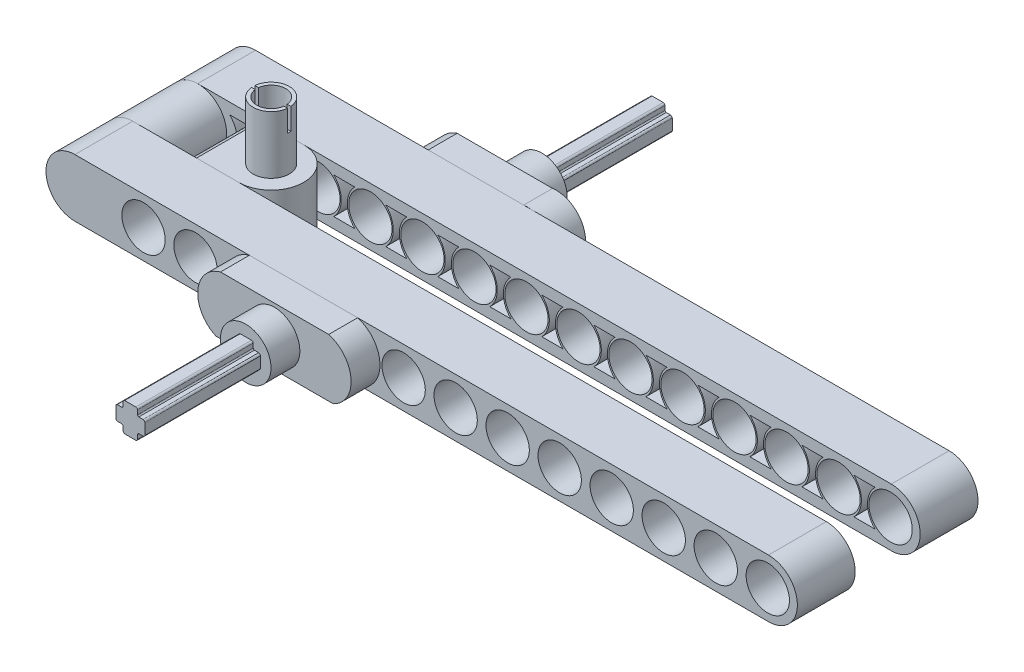
SolidWorks part; units mm, degrees
ref_plane "Front Plane" through (0, 0, 0) normal (0, 0, 1) x (1, 0, 0)
ref_plane "Top Plane" through (0, 0, 0) normal (0, 1, 0) x (1, 0, 0)
ref_plane "Right Plane" through (0, 0, 0) normal (1, 0, 0) x (0, 0, -1)
sketch "Sketch1" plane through (0, 0, 0) normal (0, 0, 1) x (1, 0, 0)
  line L1 (48, 4) -> (-48, 4)
  line L3 (48, -4) -> (-48, -4)
  line L5 (48, 4) -> (-48, -4) construction
  line L6 (48, -4) -> (-48, 4) construction
  arc A0 (48, -4) -> (48, 4) centre (48, 0) ccw
  arc A1 (-48, 4) -> (-48, -4) centre (-48, 0) ccw
  point P0 (0, 0)
  dimension "D1" = 96
  dimension "D2" = 8
extrude "Boss-Extrude1" add sketch "Sketch1" against normal blind 8
sketch "Sketch2" plane through (0, 0, 0) normal (0, 0, 1) x (1, 0, 0)
  circle A0 centre (-48, 0) radius 4
  dimension "D1" = 8
extrude "Boss-Extrude2" add sketch "Sketch2" along normal blind 9 separate body
sketch "Sketch3" plane through (0, 0, 9) normal (0, 0, 1) x (1, 0, 0)
  line L0 (48, 4) -> (-48, 4)
  line L1 (48, -4) -> (-48, -4)
  line L2 (48, 4) -> (-48, -4) construction
  line L3 (48, -4) -> (-48, 4) construction
  arc A0 (48, -4) -> (48, 4) centre (48, 0) ccw
  arc A1 (-48, 4) -> (-48, -4) centre (-48, 0) ccw
  point P0 (0, 0)
  dimension "D1" = 96
  dimension "D2" = 8
extrude "Boss-Extrude3" add sketch "Sketch3" along normal blind 8 separate body
sketch "Sketch4" plane through (0, 0, 0) normal (0, 0, 1) x (1, 0, 0)
  line L0 (-48, -4) -> (48, -4) construction
  line L1 (-39.9427, 3) -> (-42.8574, 3)
  line L2 (-39.9427, -3) -> (-42.8574, -3)
  line L3 (-32.7427, 3) -> (-35.6574, 3)
  line L4 (-32.7427, -3) -> (-35.6574, -3)
  line L5 (-25.5427, 3) -> (-28.4574, 3)
  line L6 (-25.5427, -3) -> (-28.4574, -3)
  line L7 (-18.3427, 3) -> (-21.2574, 3)
  line L8 (-18.3427, -3) -> (-21.2574, -3)
  line L9 (-11.1427, 3) -> (-14.0574, 3)
  line L10 (-11.1427, -3) -> (-14.0574, -3)
  line L11 (-3.9427, 3) -> (-6.8574, 3)
  line L12 (-3.9427, -3) -> (-6.8574, -3)
  line L13 (3.2573, 3) -> (0.3426, 3)
  line L14 (3.2573, -3) -> (0.3426, -3)
  line L15 (10.4573, 3) -> (7.5426, 3)
  line L16 (10.4573, -3) -> (7.5426, -3)
  line L17 (17.6573, 3) -> (14.7426, 3)
  line L18 (17.6573, -3) -> (14.7426, -3)
  line L19 (24.8573, 3) -> (21.9426, 3)
  line L20 (24.8573, -3) -> (21.9426, -3)
  line L21 (32.0573, 3) -> (29.1426, 3)
  line L22 (32.0573, -3) -> (29.1426, -3)
  line L23 (39.2573, 3) -> (36.3426, 3)
  line L24 (39.2573, -3) -> (36.3426, -3)
  line L25 (46.4573, 3) -> (43.5426, 3)
  line L26 (46.4573, -3) -> (43.5426, -3)
  circle A0 centre (-38.5, 0) radius 3
  circle A1 centre (-48, 0) radius 4 construction
  arc A2 (-42.8574, 3) -> (-42.8574, -3) centre (-44.7282, 0) cw
  arc A3 (-39.9427, 3) -> (-39.9427, -3) centre (-38.0718, 0) ccw
  circle A4 centre (-31.3, 0) radius 3
  arc A5 (-35.6574, 3) -> (-35.6574, -3) centre (-37.5282, 0) cw
  arc A6 (-32.7427, 3) -> (-32.7427, -3) centre (-30.8718, 0) ccw
  circle A7 centre (-24.1, 0) radius 3
  arc A8 (-28.4574, 3) -> (-28.4574, -3) centre (-30.3282, 0) cw
  arc A9 (-25.5427, 3) -> (-25.5427, -3) centre (-23.6718, 0) ccw
  circle A10 centre (-16.9, 0) radius 3
  arc A11 (-21.2574, 3) -> (-21.2574, -3) centre (-23.1282, 0) cw
  arc A12 (-18.3427, 3) -> (-18.3427, -3) centre (-16.4718, 0) ccw
  circle A13 centre (-9.7, 0) radius 3
  arc A14 (-14.0574, 3) -> (-14.0574, -3) centre (-15.9282, 0) cw
  arc A15 (-11.1427, 3) -> (-11.1427, -3) centre (-9.2718, 0) ccw
  circle A16 centre (-2.5, 0) radius 3
  arc A17 (-6.8574, 3) -> (-6.8574, -3) centre (-8.7282, 0) cw
  arc A18 (-3.9427, 3) -> (-3.9427, -3) centre (-2.0718, 0) ccw
  circle A19 centre (4.7, 0) radius 3
  arc A20 (0.3426, 3) -> (0.3426, -3) centre (-1.5282, 0) cw
  arc A21 (3.2573, 3) -> (3.2573, -3) centre (5.1282, 0) ccw
  circle A22 centre (11.9, 0) radius 3
  arc A23 (7.5426, 3) -> (7.5426, -3) centre (5.6718, 0) cw
  arc A24 (10.4573, 3) -> (10.4573, -3) centre (12.3282, 0) ccw
  circle A25 centre (19.1, 0) radius 3
  arc A26 (14.7426, 3) -> (14.7426, -3) centre (12.8718, 0) cw
  arc A27 (17.6573, 3) -> (17.6573, -3) centre (19.5282, 0) ccw
  circle A28 centre (26.3, 0) radius 3
  arc A29 (21.9426, 3) -> (21.9426, -3) centre (20.0718, 0) cw
  arc A30 (24.8573, 3) -> (24.8573, -3) centre (26.7282, 0) ccw
  circle A31 centre (33.5, 0) radius 3
  arc A32 (29.1426, 3) -> (29.1426, -3) centre (27.2718, 0) cw
  arc A33 (32.0573, 3) -> (32.0573, -3) centre (33.9282, 0) ccw
  circle A34 centre (40.7, 0) radius 3
  arc A35 (36.3426, 3) -> (36.3426, -3) centre (34.4718, 0) cw
  arc A36 (39.2573, 3) -> (39.2573, -3) centre (41.1282, 0) ccw
  circle A37 centre (47.9, 0) radius 3
  arc A38 (43.5426, 3) -> (43.5426, -3) centre (41.6718, 0) cw
  arc A39 (46.4573, 3) -> (46.4573, -3) centre (48.3282, 0) ccw
  point P12 (-41.6074, 0)
  dimension "D1" = 6
  dimension "D4" = 3.5355
  dimension "D6" = 3.5355
  dimension "D2" = 9.5
  dimension "D3" = 4
  dimension "D5" = 3.1074
  dimension "D7" = 2.9147
  dimension "D9" = 7.2
  dimension "D8" = 13
extrude "Cut-Extrude4" cut sketch "Sketch4" against normal through all both and the other way through all contours A0 | A4 | A7 | A16 | A13 | A10 | A19 | A22 | A25 | A28 | A34 | A31 | A37
sketch "Sketch12" plane through (0, 0, 0) normal (0, 0, 1) x (1, 0, 0)
  line L0 (-40.6568, 2.4796) -> (-43.5715, 2.4796)
  line L1 (-40.6568, -2.5204) -> (-43.5715, -2.5204)
  line L2 (-33.4568, 2.4796) -> (-36.3715, 2.4796)
  line L3 (-33.4568, -2.5204) -> (-36.3715, -2.5204)
  line L4 (-26.2568, 2.4796) -> (-29.1715, 2.4796)
  line L5 (-26.2568, -2.5204) -> (-29.1715, -2.5204)
  line L6 (-19.0568, 2.4796) -> (-21.9715, 2.4796)
  line L7 (-19.0568, -2.5204) -> (-21.9715, -2.5204)
  line L8 (-11.8568, 2.4796) -> (-14.7715, 2.4796)
  line L9 (-11.8568, -2.5204) -> (-14.7715, -2.5204)
  line L10 (-4.6568, 2.4796) -> (-7.5715, 2.4796)
  line L11 (-4.6568, -2.5204) -> (-7.5715, -2.5204)
  line L12 (2.5432, 2.4796) -> (-0.3715, 2.4796)
  line L13 (2.5432, -2.5204) -> (-0.3715, -2.5204)
  line L14 (9.7432, 2.4796) -> (6.8285, 2.4796)
  line L15 (9.7432, -2.5204) -> (6.8285, -2.5204)
  line L16 (16.9432, 2.4796) -> (14.0285, 2.4796)
  line L17 (16.9432, -2.5204) -> (14.0285, -2.5204)
  line L18 (24.1432, 2.4796) -> (21.2285, 2.4796)
  line L19 (24.1432, -2.5204) -> (21.2285, -2.5204)
  line L20 (31.3432, 2.4796) -> (28.4285, 2.4796)
  line L21 (31.3432, -2.5204) -> (28.4285, -2.5204)
  line L22 (38.5432, 2.4796) -> (35.6285, 2.4796)
  line L23 (38.5432, -2.5204) -> (35.6285, -2.5204)
  line L24 (45.7432, 2.4796) -> (42.8285, 2.4796)
  line L25 (45.7432, -2.5204) -> (42.8285, -2.5204)
  line L26 (-40.6568, 2.4796) -> (-33.4568, 2.4796) construction
  arc A0 (-43.5715, 2.4796) -> (-43.5715, -2.5204) centre (-46.0715, -0.0204) cw
  arc A1 (-40.6568, 2.4796) -> (-40.6568, -2.5204) centre (-38.1568, -0.0204) ccw
  arc A2 (-36.3715, 2.4796) -> (-36.3715, -2.5204) centre (-38.8715, -0.0204) cw
  arc A3 (-33.4568, 2.4796) -> (-33.4568, -2.5204) centre (-30.9568, -0.0204) ccw
  arc A4 (-29.1715, 2.4796) -> (-29.1715, -2.5204) centre (-31.6715, -0.0204) cw
  arc A5 (-26.2568, 2.4796) -> (-26.2568, -2.5204) centre (-23.7568, -0.0204) ccw
  arc A6 (-21.9715, 2.4796) -> (-21.9715, -2.5204) centre (-24.4715, -0.0204) cw
  arc A7 (-19.0568, 2.4796) -> (-19.0568, -2.5204) centre (-16.5568, -0.0204) ccw
  arc A8 (-14.7715, 2.4796) -> (-14.7715, -2.5204) centre (-17.2715, -0.0204) cw
  arc A9 (-11.8568, 2.4796) -> (-11.8568, -2.5204) centre (-9.3568, -0.0204) ccw
  arc A10 (-7.5715, 2.4796) -> (-7.5715, -2.5204) centre (-10.0715, -0.0204) cw
  arc A11 (-4.6568, 2.4796) -> (-4.6568, -2.5204) centre (-2.1568, -0.0204) ccw
  arc A12 (-0.3715, 2.4796) -> (-0.3715, -2.5204) centre (-2.8715, -0.0204) cw
  arc A13 (2.5432, 2.4796) -> (2.5432, -2.5204) centre (5.0432, -0.0204) ccw
  arc A14 (6.8285, 2.4796) -> (6.8285, -2.5204) centre (4.3285, -0.0204) cw
  arc A15 (9.7432, 2.4796) -> (9.7432, -2.5204) centre (12.2432, -0.0204) ccw
  arc A16 (14.0285, 2.4796) -> (14.0285, -2.5204) centre (11.5285, -0.0204) cw
  arc A17 (16.9432, 2.4796) -> (16.9432, -2.5204) centre (19.4432, -0.0204) ccw
  arc A18 (21.2285, 2.4796) -> (21.2285, -2.5204) centre (18.7285, -0.0204) cw
  arc A19 (24.1432, 2.4796) -> (24.1432, -2.5204) centre (26.6432, -0.0204) ccw
  arc A20 (28.4285, 2.4796) -> (28.4285, -2.5204) centre (25.9285, -0.0204) cw
  arc A21 (31.3432, 2.4796) -> (31.3432, -2.5204) centre (33.8432, -0.0204) ccw
  arc A22 (35.6285, 2.4796) -> (35.6285, -2.5204) centre (33.1285, -0.0204) cw
  arc A23 (38.5432, 2.4796) -> (38.5432, -2.5204) centre (41.0432, -0.0204) ccw
  arc A24 (42.8285, 2.4796) -> (42.8285, -2.5204) centre (40.3285, -0.0204) cw
  arc A25 (45.7432, 2.4796) -> (45.7432, -2.5204) centre (48.2432, -0.0204) ccw
  dimension "D1" = 7.2
sketch "Sketch32" plane through (0, 0, 0) normal (0, 0, 1) x (1, 0, 0)
  line L0 (-39.1605, -4) -> (-28.8284, -4)
  line L2 (-28.8284, -4) -> (-28.8284, 4)
  line L3 (-28.8284, 4) -> (-39.1605, 4)
  line L5 (-48, -4) -> (48, -4) construction
  arc A0 (-39.1605, 4) -> (-39.1605, -4) centre (-37.1812, 0) ccw
extrude "Boss-Extrude9" add sketch "Sketch32" along normal blind 9 separate body contours L3 A0 L0 L2 region at (-34.9026, 0, 0)
fillet "Fillet7" 2 edges at (-28.8284, 0, 0) (-28.8284, 0, 9) type full round first side face at (-34.6153, 0, 0) second side face at (-34.6153, 0, 9) middle face at (-28.8284, 0, 4.5)
sketch "Sketch33" plane through (0, 4, 0) normal (0, 1, 0) x (1, 0, 0)
  circle A0 centre (-33.3284, -4.5) radius 2.5
  circle A1 centre (-33.3284, -4.5) radius 2
  dimension "D1" = 5
  dimension "D2" = 4
extrude "Boss-Extrude11" add sketch "Sketch33" along normal blind 8
sketch "Sketch34" plane through (0, 12, 0) normal (0, 1, 0) x (1, 0, 0)
  line L1 (-30.7174, -4.7271) -> (-35.9394, -4.7271)
  line L2 (-30.7174, -4.7271) -> (-30.7174, -4.2729)
  line L3 (-30.7174, -4.2729) -> (-35.9394, -4.2729)
  line L4 (-35.9394, -4.7271) -> (-35.9394, -4.2729)
  line L5 (-30.7174, -4.7271) -> (-35.9394, -4.2729) construction
  line L6 (-30.7174, -4.2729) -> (-35.9394, -4.7271) construction
  point P0 (-33.3284, -4.5)
extrude "Cut-Extrude17" cut sketch "Sketch34" against normal blind 3
sketch "Sketch36" plane through (0, 0, -8) normal (0, 0, -1) x (-1, 0, 0)
  line L0 (-48, 4) -> (48, 4) construction
  line L1 (48, -4) -> (-48, -4) construction
  line L2 (10.8889, 4) -> (24.1, 4)
  line L3 (24.1, -4) -> (10.8889, -4)
  arc A0 (24.1, 4) -> (24.1, -4) centre (22.8636, 0) cw
  arc A1 (10.8889, 4) -> (10.8889, -4) centre (10.3587, 0) ccw
extrude "Boss-Extrude12" add sketch "Sketch36" along normal blind 4 separate body
sketch "Sketch41" plane through (0, 0, 17) normal (0, 0, 1) x (1, 0, 0)
  line L0 (48, 4) -> (-48, 4) construction
  line L1 (-48, -4) -> (48, -4) construction
  line L2 (-23.8503, 4) -> (-8.8716, 4)
  line L3 (-8.2565, -4) -> (-24.4875, -4)
  arc A0 (-23.8503, 4) -> (-24.4875, -4) centre (-22.7356, -0.1142) ccw
  arc A1 (-8.8716, 4) -> (-8.2565, -4) centre (-10.0491, -0.1142) cw
extrude "Boss-Extrude16" add sketch "Sketch41" along normal blind 4 separate body
sketch "Sketch43" plane through (0, 0, 21) normal (0, 0, 1) x (1, 0, 0)
  circle A0 centre (-16.3609, 0) radius 3.5
extrude "Boss-Extrude17" add sketch "Sketch43" along normal blind 4 separate body
sketch "Sketch44" plane through (0, 0, 25) normal (0, 0, 1) x (1, 0, 0)
  line L0 (-17.475, 0.9656) -> (-18.1425, 0.9656)
  line L1 (-15.5651, 1.9618) -> (-17.1236, 1.9618)
  line L2 (-15.3181, 1.7319) -> (-15.3181, 1.1485)
  line L3 (-15.5918, -2.0383) -> (-17.0381, -2.0383)
  line L4 (-17.3208, 1.7483) -> (-17.3208, 1.117)
  line L5 (-14.567, 0.9656) -> (-15.1595, 0.9656)
  line L6 (-14.3157, 0.7148) -> (-14.3157, -0.8167)
  line L7 (-14.5293, -1.035) -> (-15.1366, -1.035)
  line L8 (-18.3163, 0.7583) -> (-18.3163, -0.8642)
  line L9 (-17.513, -1.0344) -> (-18.1425, -1.0344)
  line L10 (-17.3208, -1.2093) -> (-17.3208, -1.7808)
  line L11 (-15.3181, -1.2189) -> (-15.3181, -1.7938)
  arc A0 (-17.513, -1.0344) -> (-17.3208, -1.2093) centre (-17.5334, -1.2498) cw
  arc A1 (-17.475, 0.9656) -> (-17.3208, 1.117) centre (-17.5293, 1.175) ccw
  arc A2 (-15.3181, 1.1485) -> (-15.1595, 0.9656) centre (-15.1033, 1.1745) ccw
  arc A3 (-15.1366, -1.035) -> (-15.3181, -1.2189) centre (-15.1038, -1.2489) ccw
  arc A4 (-18.1425, 0.9656) -> (-18.3163, 0.7583) centre (-18.1, 0.7534) ccw
  arc A5 (-18.3163, -0.8642) -> (-18.1425, -1.0344) centre (-18.1042, -0.8215) ccw
  arc A6 (-17.3208, -1.7808) -> (-17.0381, -2.0383) centre (-17.0406, -1.7571) ccw
  arc A7 (-15.3181, -1.7938) -> (-15.5918, -2.0383) centre (-15.5918, -1.7629) cw
  arc A8 (-14.3157, -0.8167) -> (-14.5293, -1.035) centre (-14.5671, -0.7843) cw
  arc A9 (-14.567, 0.9656) -> (-14.3157, 0.7148) centre (-14.63, 0.651) cw
  arc A10 (-15.5651, 1.9618) -> (-15.3181, 1.7319) centre (-15.5789, 1.6993) cw
  arc A11 (-17.3208, 1.7483) -> (-17.1236, 1.9618) centre (-17.0593, 1.7046) cw
  point P0 (-16.3163, -0.0383)
  point P4 (-16.3163, -0.0383)
  dimension "D1" = 2
  dimension "D2" = 2
extrude "Boss-Extrude18" add sketch "Sketch44" along normal blind 16 separate body
ref_plane "Plane2" through (0, 0, 17) normal (0, 0, 1) x (1, 0, 0)
ref_plane "Plane3" through (0, 0, 4.5) normal (0, 0, -1) x (-1, 0, 0)
mirror "Mirror3" about plane through (0, 0, 4.5) normal (0, 0, -1) of bodies 135
mirror "Mirror4" about plane through (0, 0, 4.5) normal (0, 0, -1) of bodies 134
extrude "Cut-Extrude18" cut sketch "Sketch12" against normal blind 2
